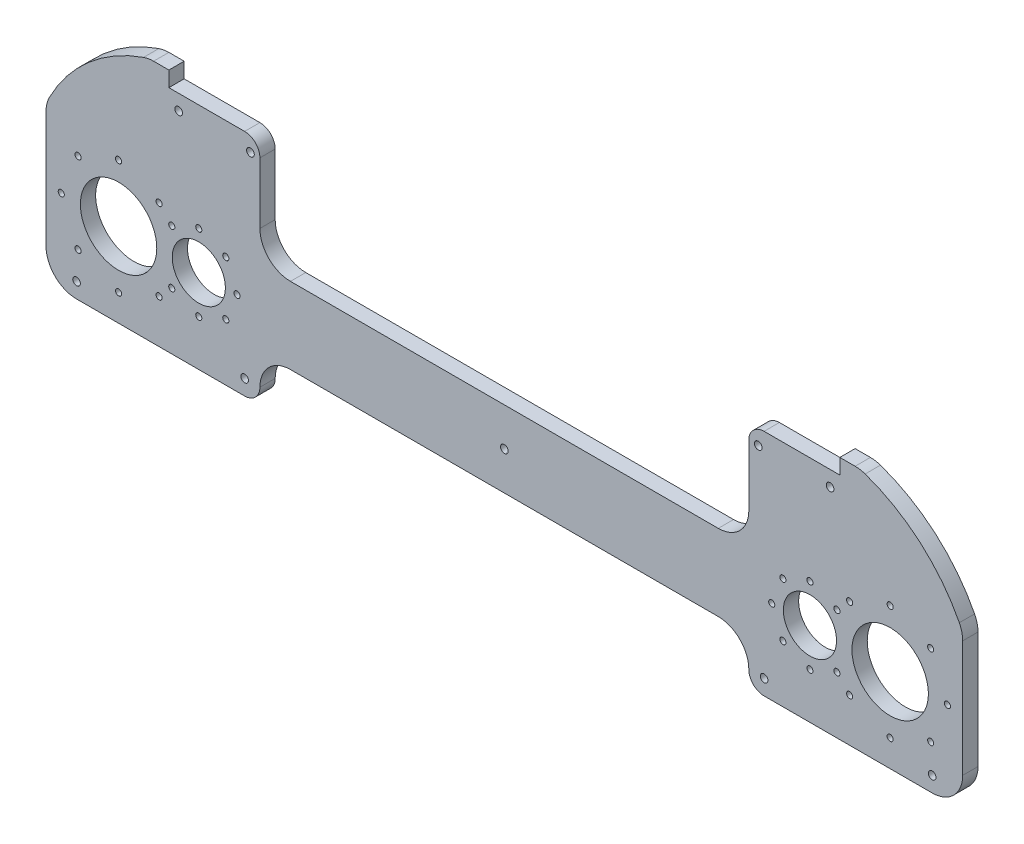
SolidWorks part; units mm, degrees
material "ABS"
ref_plane "Front Plane" through (0, 0, 0) normal (0, 0, 1) x (1, 0, 0)
ref_plane "Top Plane" through (0, 0, 0) normal (0, 1, 0) x (1, 0, 0)
ref_plane "Right Plane" through (0, 0, 0) normal (1, 0, 0) x (0, 0, -1)
sketch "Sketch1" plane through (0, 0, 0) normal (0, 0, 1) x (1, 0, 0)
  line L0 (-145.7836, 66.675) -> (145.7836, 66.675)
  line L1 (-190.5, 26.1817) -> (-190.5, -22.225)
  line L4 (0, 0) -> (0, 100.7987) construction
  line L5 (-177.8, -34.925) -> (177.8, -34.925)
  line L6 (190.5, 26.1817) -> (190.5, -22.225)
  line L7 (-190.5, 34.925) -> (190.5, -34.925) construction
  line L8 (-190.5, -34.925) -> (190.5, 34.925) construction
  arc A0 (177.8, -34.925) -> (190.5, -22.225) centre (177.8, -22.225) ccw
  arc A1 (149.9577, 65.9694) -> (189.0889, 31.9999) centre (127, 0) cw
  circle A2 centre (-127, 0) radius 3.175
  circle A3 centre (127, 0) radius 3.175
  arc A4 (-177.8, -34.925) -> (-190.5, -22.225) centre (-177.8, -22.225) cw
  arc A5 (190.5, 26.1817) -> (189.0889, 31.9999) centre (177.8, 26.1817) ccw
  arc A6 (-149.9577, 65.9694) -> (-189.0889, 31.9999) centre (-127, 0) ccw
  arc A7 (149.9577, 65.9694) -> (145.7836, 66.675) centre (145.7836, 53.975) ccw
  arc A8 (-190.5, 26.1817) -> (-189.0889, 31.9999) centre (-177.8, 26.1817) cw
  arc A9 (-145.7836, 66.675) -> (-149.9577, 65.9694) centre (-145.7836, 53.975) ccw
  point P0 (0, 0)
  point P22 (190.5, 29.0994)
  point P27 (147.8199, 66.675)
  point P30 (-190.5, 29.0994)
  point P33 (-147.8199, 66.675)
  dimension "D3" = 6.35
  dimension "D4" = 6.35
  dimension "D6" = 66.675
  dimension "D7" = 12.7
  dimension "D2" = 381
  dimension "D5" = 12.7
  dimension "D1" = 69.85
  dimension "D8" = 139.7
extrude "Boss-Extrude1" add sketch "Sketch1" along normal mid plane 6.35
sketch "Sketch2" plane through (0, 0, 3.175) normal (0, 0, 1) x (1, 0, 0)
  line L0 (-127, 0) -> (-207.737, 0) construction
  line L1 (127, 0) -> (207.737, 0) construction
  line L4 (0, 0) -> (0, 93.9723) construction
  circle A0 centre (-127, 0) radius 11.049
  circle A1 centre (-160.3375, 0) radius 15.875
  circle A2 centre (-143.4995, 16.838) radius 1.27
  circle A3 centre (-136.525, 0) radius 1.27 [skipped]
  circle A4 centre (-160.3375, 0) radius 23.8125 construction
  circle A5 centre (-127, 0) radius 15.875 construction
  circle A6 centre (-160.3375, 23.8125) radius 1.27
  circle A7 centre (-143.4995, -16.838) radius 1.27
  circle A8 centre (-160.3375, -23.8125) radius 1.27
  circle A9 centre (-177.1755, -16.838) radius 1.27
  circle A10 centre (-184.15, 0) radius 1.27
  circle A11 centre (-177.1755, 16.838) radius 1.27
  circle A12 centre (127, 0) radius 15.875 construction
  circle A13 centre (160.3375, 0) radius 23.8125 construction
  circle A14 centre (-127, 15.875) radius 1.27
  circle A15 centre (-115.7747, 11.2253) radius 1.27
  circle A16 centre (-111.125, 0) radius 1.27
  circle A17 centre (-115.7747, -11.2253) radius 1.27
  circle A18 centre (-127, -15.875) radius 1.27
  circle A19 centre (-138.2253, -11.2253) radius 1.27
  circle A20 centre (138.2253, 11.2253) radius 1.27
  circle A21 centre (-138.2253, 11.2253) radius 1.27
  circle A22 centre (-142.875, 0) radius 1.27 [skipped]
  circle A23 centre (138.2253, -11.2253) radius 1.27
  circle A24 centre (127, -15.875) radius 1.27
  circle A25 centre (115.7747, -11.2253) radius 1.27
  circle A26 centre (111.125, 0) radius 1.27
  circle A27 centre (115.7747, 11.2253) radius 1.27
  circle A28 centre (127, 15.875) radius 1.27
  circle A29 centre (177.1755, 16.838) radius 1.27
  circle A30 centre (184.15, 0) radius 1.27
  circle A31 centre (177.1755, -16.838) radius 1.27
  circle A32 centre (160.3375, -23.8125) radius 1.27
  circle A33 centre (143.4995, -16.838) radius 1.27
  circle A34 centre (160.3375, 23.8125) radius 1.27
  circle A35 centre (143.4995, 16.838) radius 1.27
  circle A36 centre (160.3375, 0) radius 15.875
  circle A37 centre (127, 0) radius 11.049
  dimension "D2" = 33.3375
  dimension "D3" = 31.75
  dimension "D4" = 31.75
  dimension "D5" = 47.625
  dimension "D6" = 2.54
  dimension "D1" = 22.098
  dimension "D8" = 2.54
  dimension "D7" = 8
  dimension "D9" = 8
extrude "Cut-Extrude1" cut sketch "Sketch2" against normal through all
sketch "Sketch5" plane through (0, 0, 3.175) normal (0, 0, 1) x (1, 0, 0)
  line L0 (145.7836, 66.675) -> (-145.7836, 66.675) construction
  line L1 (-88.9, 15.875) -> (88.9, 15.875)
  line L2 (-101.6, 28.575) -> (-101.6, 66.675)
  line L3 (-101.6, 66.675) -> (101.6, 66.675)
  line L4 (101.6, 28.575) -> (101.6, 66.675)
  line L5 (-101.6, 15.875) -> (101.6, 66.675) construction
  line L6 (-101.6, 66.675) -> (101.6, 15.875) construction
  line L7 (0, 0) -> (0, 128.2224) construction
  arc A0 (101.6, 28.575) -> (88.9, 15.875) centre (88.9, 28.575) cw
  arc A1 (-88.9, 15.875) -> (-101.6, 28.575) centre (-88.9, 28.575) cw
  point P0 (0, 41.275)
  dimension "D3" = 12.7
  dimension "D1" = 50.8
  dimension "D2" = 203.2
extrude "ITC_Cutout" cut sketch "Sketch5" against normal through all
sketch "Sketch6" plane through (0, 0, 3.175) normal (0, 0, 1) x (1, 0, 0)
  line L0 (-101.6, 66.675) -> (-145.7836, 66.675) construction
  line L1 (-71.9103, 66.675) -> (-139.4336, 66.675)
  line L2 (-71.9103, 66.675) -> (-71.9103, 60.325)
  line L3 (-71.9103, 60.325) -> (-139.4336, 60.325)
  line L4 (-139.4336, 66.675) -> (-139.4336, 60.325)
  line L5 (0, 0) -> (0, 132.6418) construction
  line L6 (139.4336, 66.675) -> (139.4336, 60.325)
  line L7 (71.9103, 60.325) -> (139.4336, 60.325)
  line L8 (71.9103, 66.675) -> (71.9103, 60.325)
  line L9 (71.9103, 66.675) -> (139.4336, 66.675)
  dimension "D1" = 6.35
  dimension "D2" = 6.35
extrude "Cut-Extrude3" cut sketch "Sketch6" against normal through all
fillet "Fillet1" radius 6.35 2 edges at (101.6, 60.325, 0) (-101.6, 60.325, 0)
sketch "Sketch7" plane through (0, 0, 3.175) normal (0, 0, 1) x (1, 0, 0)
  line L0 (0, 38.9819) -> (0, -79.3414) construction
  line L1 (-177.8, -34.925) -> (177.8, -34.925) construction
  line L2 (-88.9, -15.875) -> (88.9, -15.875)
  line L3 (-101.6, -28.575) -> (-101.6, -34.925)
  line L4 (-101.6, -34.925) -> (101.6, -34.925)
  line L5 (101.6, -28.575) -> (101.6, -34.925)
  line L6 (-101.6, -15.875) -> (101.6, -34.925) construction
  line L7 (-101.6, -34.925) -> (101.6, -15.875) construction
  line L8 (-101.6, 53.975) -> (-101.6, 28.575) construction
  arc A0 (101.6, -28.575) -> (88.9, -15.875) centre (88.9, -28.575) ccw
  arc A1 (-88.9, -15.875) -> (-101.6, -28.575) centre (-88.9, -28.575) ccw
  point P3 (0, -25.4)
  dimension "D2" = 12.7
  dimension "D1" = 19.05
extrude "Cut-Extrude4" cut sketch "Sketch7" against normal through all
fillet "Fillet2" radius 6.35 2 edges at (101.6, -34.925, 0) (-101.6, -34.925, 0)
sketch "Sketch8" plane through (0, 0, 3.175) normal (0, 0, 1) x (1, 0, 0)
  line L0 (-139.4336, 60.325) -> (-107.95, 60.325) construction
  line L1 (-139.4336, 66.675) -> (-139.4336, 60.325) construction
  line L2 (0, 0) -> (0, 74.8203) construction
  circle A0 centre (-135.3696, 53.975) radius 1.5875
  circle A1 centre (-105.5246, 53.975) radius 1.5875
  circle A2 centre (105.5246, 53.975) radius 1.5875
  circle A3 centre (135.3696, 53.975) radius 1.5875
  dimension "D1" = 3.175
  dimension "D3" = 3.175
  dimension "D2" = 6.35
  dimension "D4" = 29.845
  dimension "D5" = 4.064
extrude "Cut-Extrude5" cut sketch "Sketch8" against normal through all
sketch "Sketch10" plane through (0, 0, 3.175) normal (0, 0, 1) x (1, 0, 0)
  line L0 (0, 50.0636) -> (0, -61.6077) construction
  line L1 (-177.8, -34.925) -> (-107.95, -34.925) construction
  circle A0 centre (-177.8, -28.575) radius 1.5875
  circle A1 centre (-107.95, -28.575) radius 1.5875
  circle A2 centre (107.95, -28.575) radius 1.5875
  circle A3 centre (177.8, -28.575) radius 1.5875
  circle A4 centre (0, 0) radius 1.5875
  dimension "D1" = 3.175
  dimension "D4" = 3.175
  dimension "D6" = 3.175
  dimension "D2" = 6.35
  dimension "D3" = 177.8
  dimension "D5" = 107.95
extrude "Cut-Extrude6" cut sketch "Sketch10" against normal through all
equation "\"D3@Sketch8\" = \"D1@Sketch8\""
